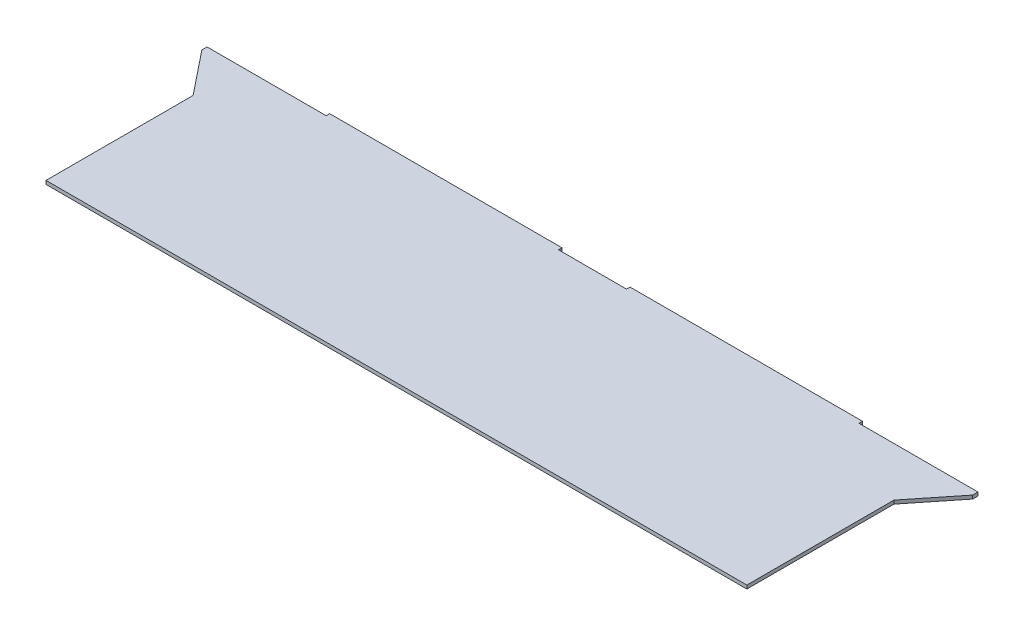
SolidWorks part; units mm, degrees
material "6061-T6 (SS)"
ref_plane "X-Y Datum" through (0, 0, 0) normal (0, 0, 1) x (1, 0, 0)
ref_plane "X-Z Datum" through (0, 0, 0) normal (0, 1, 0) x (1, 0, 0)
ref_plane "Y-Z Datum" through (0, 0, 0) normal (1, 0, 0) x (0, 0, -1)
sketch "Sketch1" plane through (0, 0, 0) normal (0, 1, 0) x (1, 0, 0)
  line L1 (-317.6778, 88.9) -> (317.6778, 88.9)
  line L2 (-317.6778, 88.9) -> (-317.6778, -88.9)
  line L3 (-317.6778, -88.9) -> (317.6778, -88.9)
  line L4 (317.6778, 88.9) -> (317.6778, -88.9)
  line L5 (-317.6778, 88.9) -> (317.6778, -88.9) construction
  line L6 (-317.6778, -88.9) -> (317.6778, 88.9) construction
  point P0 (0, 0)
  dimension "D1" = 635.3556
  dimension "D2" = 177.8
extrude "Boss-Extrude1" add sketch "Sketch1" along normal mid plane 3.175
sketch "Sketch2" plane through (0, 0, -88.9) normal (0, 0, -1) x (-1, 0, 0)
  line L0 (-241.4778, -1.5875) -> (-241.4778, 1.5875) construction
  line L1 (241.4778, -1.5875) -> (241.4778, 1.5875)
  line L2 (-241.4778, -1.5875) -> (-241.4778, 1.5875)
  line L3 (-241.4778, -1.5875) -> (-241.4778, 1.5875)
  line L4 (241.4778, -1.5875) -> (241.4778, 1.5875) construction
  line L5 (241.4778, -1.5875) -> (241.4778, 1.5875)
  line L20 (-317.6778, -1.5875) -> (317.6778, -1.5875) construction
  line L21 (-241.4778, -1.5875) -> (-30.8229, -1.5875)
  line L22 (30.8229, -1.5875) -> (241.4778, -1.5875)
  line L40 (30.8229, -1.5875) -> (30.8229, 1.5875)
  line L41 (30.8229, 1.5875) -> (241.4778, 1.5875)
  line L57 (-241.4778, 1.5875) -> (-30.8229, 1.5875)
  line L58 (-30.8229, 1.5875) -> (-30.8229, -1.5875)
  line M22 (-317.6778, -1.5875) -> (317.6778, -1.5875)
  line M24 (317.6778, 1.5875) -> (-317.6778, 1.5875)
extrude "Boss-Extrude2" add sketch "Sketch2" along normal blind 3.175 contours L58 L2 M24 M22 | L40 L1 M22 M24 region at (-136.1504, 0, -88.9) region at (136.1504, 0, -88.9)
sketch "Sketch3" plane through (0, 1.5875, 0) normal (0, 1, 0) x (1, 0, 0)
  line L0 (-317.6778, 88.9) -> (-349.4278, 88.9)
  line L1 (-349.4278, 88.9) -> (-349.4278, 84.1375)
  line L2 (-349.4278, 84.1375) -> (-317.6778, 44.45)
  line L3 (-317.6778, 88.9) -> (-317.6778, -88.9) construction
  line L16 (317.6778, -88.9) -> (317.6778, 88.9)
  line L17 (317.6778, 88.9) -> (241.4778, 88.9)
  line L18 (241.4778, 88.9) -> (241.4778, 92.075)
  line L19 (30.8229, 92.075) -> (30.8229, 88.9)
  line L20 (30.8229, 88.9) -> (-30.8229, 88.9)
  line L21 (-30.8229, 88.9) -> (-30.8229, 92.075)
  line L22 (-241.4778, 92.075) -> (-241.4778, 88.9)
  line L23 (-241.4778, 88.9) -> (-317.6778, 88.9)
  line L24 (241.4778, 92.075) -> (30.8229, 92.075)
  line L25 (241.4778, 92.075) -> (30.8229, 92.075)
  line L26 (-317.6778, 88.9) -> (-317.6778, -88.9)
  line L27 (-317.6778, -88.9) -> (317.6778, -88.9)
  line L38 (-317.6778, 88.9) -> (-317.6778, 44.45)
  line L40 (-30.8229, 92.075) -> (-241.4778, 92.075)
  line L41 (-30.8229, 92.075) -> (-241.4778, 92.075)
  line M26 (-317.6778, 88.9) -> (-317.6778, -88.9)
  dimension "D1" = 31.75
  dimension "D2" = 4.7625
  dimension "D3" = 44.45
  dimension "D4" = 0
extrude "Boss-Extrude3" add sketch "Sketch3" against normal blind 3.175 contours L1 L2 L0 M26 region at (-329.2853, 1.5875, -73.9297)
mirror "Mirror1" about plane through (0, 0, 0) normal (1, 0, 0) of "Boss-Extrude3"
